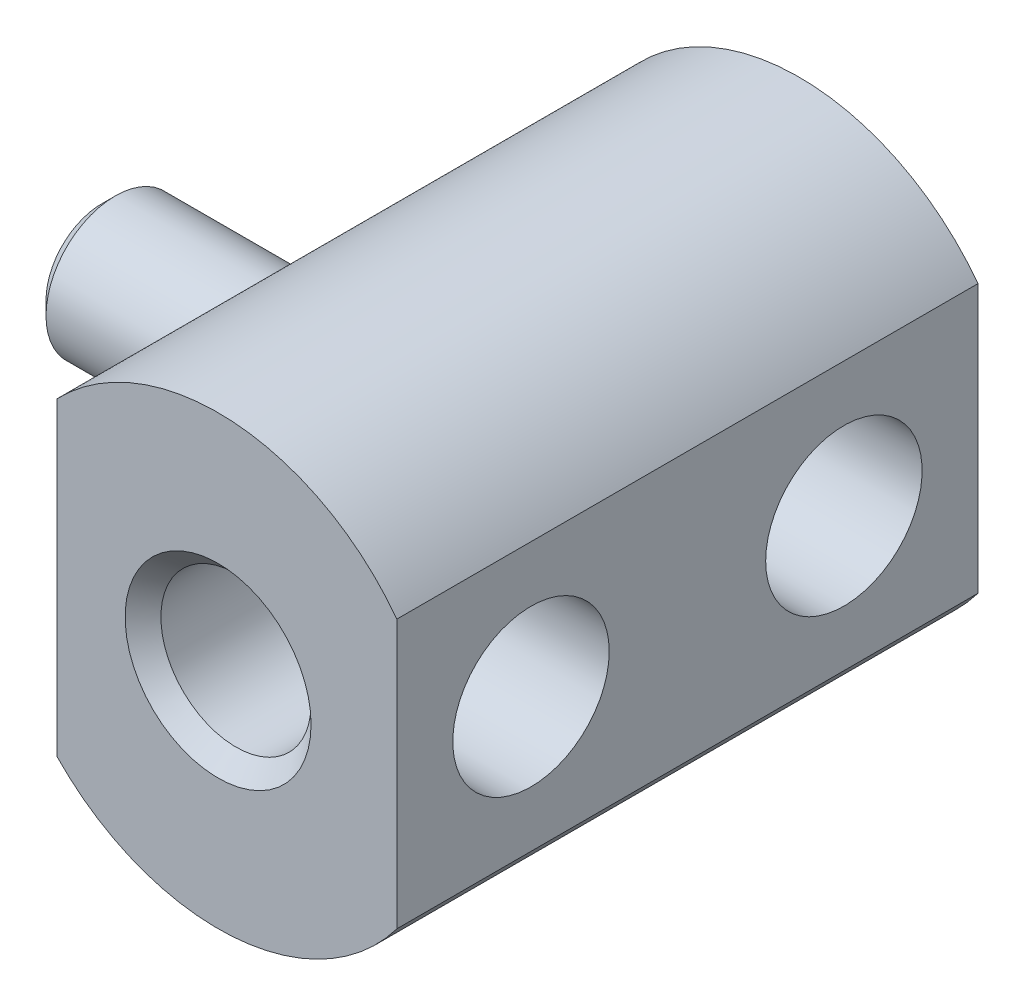
SolidWorks part; units mm, degrees
material "PLA2"
ref_plane "Front Plane" through (0, 0, 0) normal (0, 0, 1) x (1, 0, 0)
ref_plane "Top Plane" through (0, 0, 0) normal (0, 1, 0) x (1, 0, 0)
ref_plane "Right Plane" through (0, 0, 0) normal (1, 0, 0) x (0, 0, -1)
sketch "Sketch1" plane through (0, 0, 0) normal (0, 0, 1) x (1, 0, 0)
  circle A0 centre (0, 0) radius 2.1336
  circle A1 centre (0, 0) radius 6.35
  dimension "D1" = 4.2672
  dimension "D2" = 12.7
extrude "Boss-Extrude1" add sketch "Sketch1" along normal mid plane 16.51
sketch "Sketch3" plane through (0, 0, 8.255) normal (0, 0, 1) x (1, 0, 0)
  line L0 (-4.572, 4.4067) -> (-4.572, -4.4067)
  line L1 (0, 0.0885) -> (0, 50000.0885) construction
  line L3 (5.08, 3.81) -> (5.08, -3.81)
  line L4 (5.08, 0) -> (6.35, 0) construction
  arc A0 (-4.572, 4.4067) -> (-4.572, -4.4067) centre (0, 0) ccw
  arc A2 (5.08, -3.81) -> (5.08, 3.81) centre (0, 0) ccw
  circle A3 centre (0, 0) radius 6.35 construction
  point P1 (-6.35, 0)
  dimension "D1" = 1.778
  dimension "D2" = 1.27
extrude "Cut-Extrude1" cut sketch "Sketch3" against normal through all
sketch "Sketch4" plane through (-4.572, 0, 0) normal (-1, 0, 0) x (0, 0, 1)
  circle A0 centre (0, 0) radius 1.9685
  dimension "D1" = 3.937
extrude "Boss-Extrude2" add sketch "Sketch4" along normal blind 6.985
fillet "Fillet1" radius 1.27 1 edges at (-4.572, 0, 1.9685)
chamfer "Chamfer1" distance 0.381 angle 45 1 edges at (-11.557, 0, 1.9685)
sketch "Sketch5" plane through (5.08, 0, 0) normal (1, 0, 0) x (0, 0, -1)
  line L0 (0, 0) -> (0, 50000) construction
  line L1 (-4.445, 0) -> (0, 0) construction
  circle A0 centre (-4.445, 0) radius 2.2225
  circle A1 centre (4.445, 0) radius 2.2225
  dimension "D1" = 4.445
  dimension "D2" = 8.89
extrude "Cut-Extrude2" cut sketch "Sketch5" against normal blind 4.445
chamfer "Chamfer2" distance 0.508 angle 45 2 edges at (2.1336, 0, -8.255) (2.1336, 0, 8.255)
